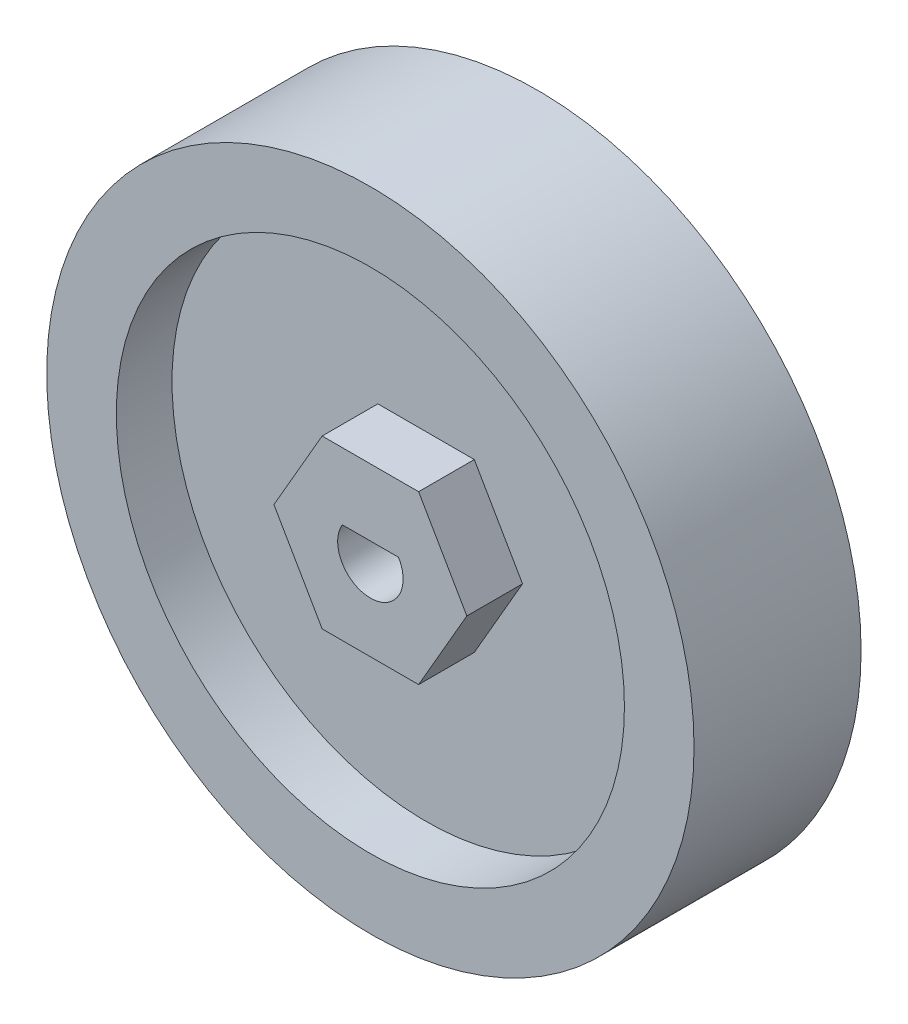
SolidWorks part; units mm, degrees
ref_plane "Plan de face" through (0, 0, 0) normal (0, 0, 1) x (1, 0, 0)
ref_plane "Plan de dessus" through (0, 0, 0) normal (0, 1, 0) x (1, 0, 0)
ref_plane "Plan de droite" through (0, 0, 0) normal (1, 0, 0) x (0, 0, -1)
sketch "Esquisse1" plane through (0, 0, 0) normal (0, 0, 1) x (1, 0, 0)
  circle A0 centre (0, 0) radius 23.25
  circle A1 centre (0, 0) radius 18.25
  dimension "D1" = 46.5
  dimension "D2" = 5
extrude "Boss.-Extru.1" add sketch "Esquisse1" along normal mid plane 12
sketch "Esquisse2" plane through (0, 0, 0) normal (0, 0, 1) x (1, 0, 0)
  circle A0 centre (0, 0) radius 18.25
  circle A1 centre (0, 0) radius 18.25 construction
extrude "Boss.-Extru.2" add sketch "Esquisse2" along normal mid plane 4
sketch "Esquisse3" plane through (0, 0, 0) normal (0, 0, 1) x (1, 0, 0)
  line L1 (-3.4641, 6) -> (-6.9282, 0)
  line L2 (-6.9282, 0) -> (-3.4641, -6)
  line L3 (-3.4641, -6) -> (3.4641, -6)
  line L4 (3.4641, -6) -> (6.9282, 0)
  line L5 (6.9282, 0) -> (3.4641, 6)
  line L6 (3.4641, 6) -> (-3.4641, 6)
  line L7 (6.6, 0) -> (-6.6, 0) construction
  circle A0 centre (0, 0) radius 6 construction
  dimension "D1" = 12
extrude "Boss.-Extru.3" add sketch "Esquisse3" along normal blind 6
sketch "Esquisse5" plane through (0, 0, 0) normal (0, 0, 1) x (1, 0, 0)
  circle A0 centre (0, 0) radius 2.35
  dimension "D1" = 4.7
extrude "Enlèv. mat.-Extru.1" cut sketch "Esquisse5" against normal mid plane 12
sketch "Esquisse6" plane through (0, 0, 0) normal (0, 0, 1) x (1, 0, 0)
  line L0 (-2.0205, 1.2) -> (2.0205, 1.2)
  arc A0 (-2.0205, 1.2) -> (2.0205, 1.2) centre (0, 0) cw
  circle A1 centre (0, 0) radius 2.35 construction
  dimension "D1" = 1.2
extrude "Boss.-Extru.5" add sketch "Esquisse6" along normal up to surface (6 mm away) up to face at (2.35, 0, 6)
